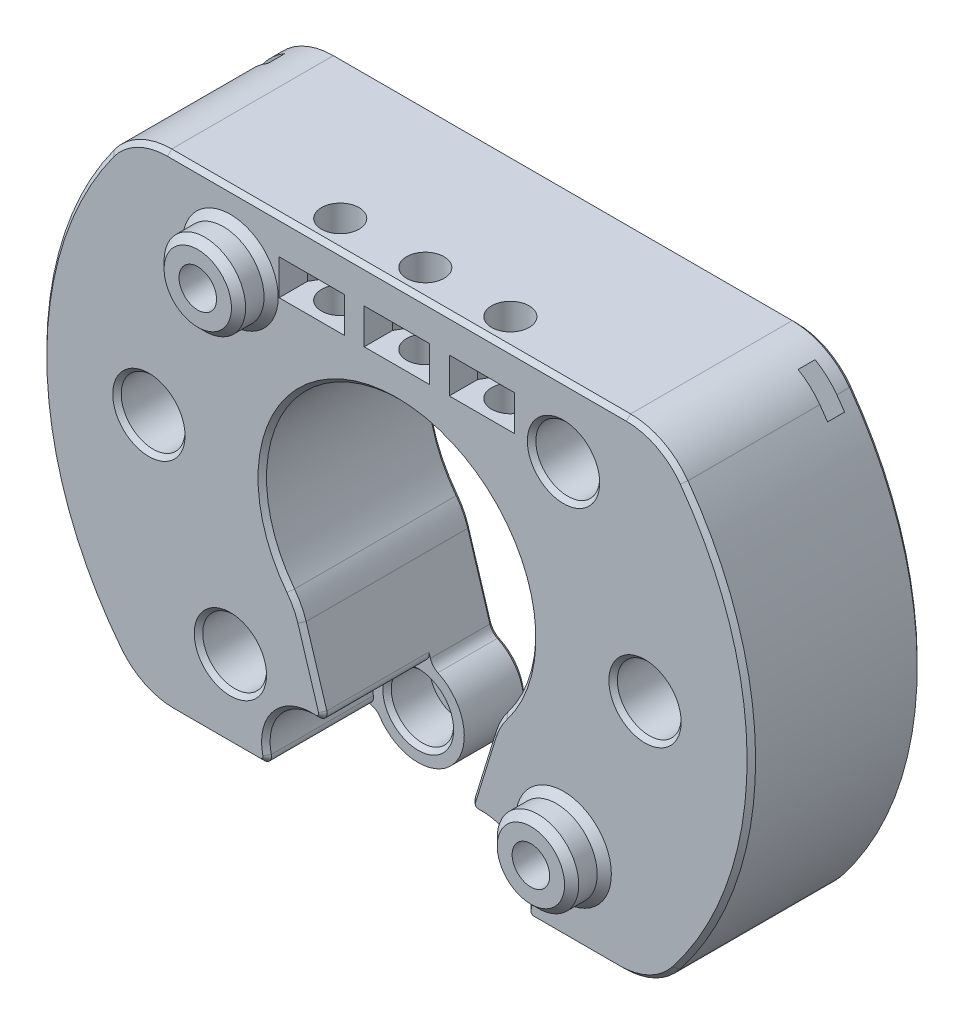
SolidWorks part; units mm, degrees
ref_plane "Ebene vorne" through (0, 0, 0) normal (0, 0, 1) x (1, 0, 0)
ref_plane "Ebene oben" through (0, 0, 0) normal (0, 1, 0) x (1, 0, 0)
ref_plane "Ebene rechts" through (0, 0, 0) normal (1, 0, 0) x (0, 0, -1)
sketch "Skizze1" plane through (0, 0, 0) normal (0, 0, 1) x (1, 0, 0)
  line L0 (0, 15.499) -> (0, -28.3741) construction
  line L1 (0, 33.5) -> (-37.1181, 33.5)
  line L2 (0, 33.5) -> (37.1181, 33.5)
  line L3 (-36, -34.6987) -> (-36, -65)
  line L4 (-36, -65) -> (0, -65)
  line L5 (-50, 78.1636) -> (-50, -33.9451) construction
  line L6 (50, 78.1636) -> (50, -33.9451) construction
  line L7 (-50, 0) -> (50, 0) construction
  line L8 (36, -34.6987) -> (36, -65)
  line L10 (0, -65) -> (36, -65)
  line L11 (-17.9133, -34.6987) -> (-36, -34.6987)
  line L12 (-23.5, 23.5) -> (23.5, 23.5) construction
  line L13 (-23.5, 23.5) -> (-23.5, -23.5) construction
  line L14 (-23.5, -23.5) -> (23.5, -23.5) construction
  line L15 (23.5, 23.5) -> (23.5, -23.5) construction
  line L18 (-14, -12.8452) -> (-10, -25.8153)
  line L19 (14, -12.8452) -> (10, -25.8153)
  line L22 (36, -34.6987) -> (17.9133, -34.6987)
  arc A0 (-37.1181, 33.5) -> (-36, -34.6987) centre (0, 0) ccw
  circle A1 centre (0, 0) radius 19
  arc A3 (37.1181, 33.5) -> (36, -34.6987) centre (0, 0) cw
  circle A4 centre (-23.5, 23.5) radius 4.5
  circle A5 centre (23.5, 23.5) radius 4.5
  circle A6 centre (23.5, -23.5) radius 4.5
  circle A7 centre (-23.5, -23.5) radius 4.5
  arc A8 (-10, -25.8153) -> (-17.9133, -34.6987) centre (-12, -32) cw
  arc A9 (10, -25.8153) -> (17.9133, -34.6987) centre (12, -32) ccw
  circle A10 centre (23.5, -23.5) radius 4.5
  point P18 (0, 0)
  point P37 (-23.5, 0)
  point P38 (0, 23.5)
  dimension "D1" = 72
  dimension "D4" = 38
  dimension "D2" = 47
  dimension "D7" = 9
  dimension "D8" = 28
  dimension "D13" = 32
  dimension "D10" = 6.5
  dimension "D3" = 65
  dimension "D5" = 33.5
  dimension "D6" = 100
  dimension "D9" = 24
  dimension "D14" = 20
extrude "Aufsatz-Linear austragen1" add sketch "Skizze1" along normal blind 24 contours L19 A9 L22 A3 L2 L1 A0 A8 L18 A1 A7 A6 A5 A4 region at (18.559, 32.2678, 0)
sketch "Skizze2" plane through (0, 0, 24) normal (0, 0, 1) x (1, 0, 0)
  line L3 (0, 0) -> (0, -32) construction
  circle A0 centre (12, -32) radius 6.5
  arc A1 (10, -25.8153) -> (17.9133, -34.6987) centre (12, -32) ccw construction
  circle A3 centre (-12, -32) radius 6.5
  arc A4 (-17.9133, -34.6987) -> (-10, -25.8153) centre (-12, -32) ccw construction
extrude "Schnitt-Linear austragen1" cut sketch "Skizze2" against normal blind 15
sketch "Skizze3" plane through (0, 0, 9) normal (0, 0, 1) x (1, 0, 0)
  circle A0 centre (12, -32) radius 4.4
  circle A1 centre (-12, -32) radius 4.4
  dimension "D1" = 8.8
extrude "Schnitt-Linear austragen2" cut sketch "Skizze3" against normal blind 6
sketch "Skizze4" plane through (0, 0, 24) normal (0, 0, 1) x (1, 0, 0)
  circle A0 centre (-23.5, 23.5) radius 5.75
  circle A1 centre (23.5, -23.5) radius 5.75
  circle A6 centre (-23.5, 23.5) radius 2.65
  circle A7 centre (23.5, -23.5) radius 2.65
  dimension "D1" = 11.5
  dimension "D2" = 5.3
extrude "Aufsatz-Linear austragen2" add sketch "Skizze4" along normal blind 4.6 and the other way blind 2
sketch "Skizze8" plane through (0, 33.5, 0) normal (0, 1, 0) x (1, 0, 0)
  line L0 (-37.1181, -24) -> (37.1181, -24) construction
  line L1 (4.6188, -20) -> (2.3094, -16)
  line L2 (2.3094, -16) -> (-2.3094, -16)
  line L3 (-2.3094, -16) -> (-4.6188, -20)
  line L4 (-4.6188, -20) -> (-2.3094, -24) construction
  line L5 (-2.3094, -24) -> (2.3094, -24) construction
  line L6 (2.3094, -24) -> (4.6188, -20) construction
  line L7 (-4.6188, -20) -> (-4.6188, -24)
  line L8 (-4.6188, -24) -> (4.6188, -24)
  line L9 (4.6188, -24) -> (4.6188, -20)
  line L10 (0, 0) -> (0, -24) construction
  line L11 (-37.1181, 0) -> (37.1181, 0) construction
  line L18 (16.6188, -20) -> (14.3094, -16)
  line L19 (14.3094, -16) -> (9.6906, -16)
  line L20 (9.6906, -16) -> (7.3812, -20)
  line L21 (7.3812, -20) -> (7.3812, -24)
  line L22 (7.3812, -24) -> (16.6188, -24)
  line L23 (16.6188, -24) -> (16.6188, -20)
  line L24 (7.3812, -20) -> (9.6906, -24) construction
  line L25 (9.6906, -24) -> (14.3094, -24) construction
  line L26 (14.3094, -24) -> (16.6188, -20) construction
  line L27 (4.6188, -20) -> (16.6188, -20) construction
  line L28 (-7.3812, -20) -> (-9.6906, -16)
  line L29 (-9.6906, -16) -> (-14.3094, -16)
  line L30 (-14.3094, -16) -> (-16.6188, -20)
  line L31 (-16.6188, -20) -> (-16.6188, -24)
  line L32 (-16.6188, -24) -> (-7.3812, -24)
  line L33 (-7.3812, -24) -> (-7.3812, -20)
  line L34 (-16.6188, -20) -> (-14.3094, -24) construction
  line L35 (-14.3094, -24) -> (-9.6906, -24) construction
  line L36 (-9.6906, -24) -> (-7.3812, -20) construction
  line L37 (4.6188, -20) -> (-7.3812, -20) construction
  circle A0 centre (0, -20) radius 4 construction
  circle A1 centre (12, -20) radius 4 construction
  circle A2 centre (-12, -20) radius 4 construction
  dimension "D1" = 8
  dimension "D2" = 2
  dimension "D3" = 12
  dimension "D4" = 12
extrude "Schnitt-Linear austragen6" cut sketch "Skizze8" against normal blind 5 from offset 5 offset against normal yes
sketch "Skizze9" plane through (0, 33.5, 0) normal (0, 1, 0) x (1, 0, 0)
  circle A0 centre (-12, -20) radius 2.65
  circle A1 centre (0, -20) radius 2.65
  circle A2 centre (12, -20) radius 2.65
  dimension "D1" = 5.3
extrude "Schnitt-Linear austragen7" cut sketch "Skizze9" against normal blind 30
sketch "Skizze12" plane through (0, 0, 0) normal (0, 0, -1) x (-1, 0, 0)
  line L0 (0, 0) -> (0, 33.5) construction
  line L1 (37.1181, 33.5) -> (-37.1181, 33.5) construction
  circle A0 centre (-35, 25.5) radius 1.65
  circle A1 centre (35, 25.5) radius 1.65
  dimension "D1" = 3.3
  dimension "D2" = 70
  dimension "D3" = 8
extrude "Schnitt-Linear austragen9" cut sketch "Skizze12" against normal blind 16
sketch "Skizze11" plane through (0, 0, 0) normal (0, 0, -1) x (-1, 0, 0)
  line L0 (0, 0) -> (0, 33.5) construction
  line L1 (37.1181, 33.5) -> (-37.1181, 33.5) construction
  line L2 (-44.8995, 39.6421) -> (-30.7574, 25.5)
  line L3 (-30.7574, 25.5) -> (-35, 21.2574)
  line L4 (-44.8995, 39.6421) -> (-49.1421, 35.3995)
  line L5 (-49.1421, 35.3995) -> (-35, 21.2574)
  line L6 (44.8995, 39.6421) -> (49.1421, 35.3995)
  line L7 (44.8995, 39.6421) -> (30.7574, 25.5)
  line L8 (30.7574, 25.5) -> (35, 21.2574)
  line L9 (49.1421, 35.3995) -> (35, 21.2574)
  dimension "D1" = 45
  dimension "D2" = 6
  dimension "D3" = 20
extrude "Schnitt-Linear austragen8" cut sketch "Skizze11" against normal blind 2.4 from offset 2.4 offset against normal yes
sketch "Skizze13" plane through (0, 0, 24) normal (0, 0, 1) x (1, 0, 0)
  line L0 (0, 33.5) -> (0, 0) construction
  line L1 (-37.1181, 33.5) -> (37.1181, 33.5) construction
  circle A0 centre (35, 0) radius 4.5
  circle A1 centre (-35, 0) radius 4.5
  dimension "D1" = 70
  dimension "D2" = 9
extrude "Schnitt-Linear austragen10" cut sketch "Skizze13" against normal up to next
chamfer "Fase1" distance 1 angle 45 4 edges at (29.25, -23.5, 28.6) (-17.75, 23.5, 28.6) (29.25, -23.5, 24) (-17.75, 23.5, 24)
fillet "Verrundung1" radius 10 6 edges at (-37.1181, 33.5, 12) (37.1181, 33.5, 12) (36, -34.6987, 12) (-36, -34.6987, 12) (14, -12.8452, 12) (-14, -12.8452, 12)
fillet "Verrundung2" radius 1 4 edges at (17.9133, -34.6987, 16.5) (-17.9133, -34.6987, 16.5) (-10, -25.8153, 16.5) (10, -25.8153, 16.5)
fillet "Verrundung4" radius 2 4 edges at (17.9133, -34.6987, 4.5) (10, -25.8153, 4.5) (-10, -25.8153, 4.5) (-17.9133, -34.6987, 4.5)
chamfer "Fase2" distance 0.6 angle 45 26 edges at (16.9372, -27.7723, 24) (25.3845, -34.6987, 24) (49.9912, -0.9388, 24) (0, 33.5, 24) (0, 19, 24) (-25.3845, -34.6987, 24) (-49.9912, -0.9388, 24) (35.8373, -33.6917, 24) (36.9104, 32.4093, 24) (-36.9104, 32.4093, 24) (-35.8373, -33.6917, 24) (28, 23.5, 24) (-19, -23.5, 24) (16.4, -32, 9) (18.522, -34.3206, 24) (11.9495, -19.4941, 24) (10.6637, -25.1437, 24) (-11.9495, -19.4941, 24) (-10.6637, -25.1437, 24) (-16.9372, -27.7723, 24) (-18.522, -34.3206, 24) (-7.6, -32, 9) (14.0856, -13.1092, 24) (-14.0856, -13.1092, 24) (39.5, 0, 24) (-39.5, 0, 24)
chamfer "Fase3" distance 0.6 angle 45 28 edges at (-35.8373, -33.6917, 0) (-25.2735, -34.6987, 0) (-7.0841, -36.2525, 0) (-11.845, -19.833, 0) (0, 19, 0) (11.845, -19.833, 0) (7.0841, -36.2525, 0) (25.2735, -34.6987, 0) (35.8373, -33.6917, 0) (49.9912, -0.9388, 0) (36.9104, 32.4093, 0) (0, 33.5, 0) (-36.9104, 32.4093, 0) (-49.9912, -0.9388, 0) (-19, 23.5, 0) (28, 23.5, 0) (28, -23.5, 0) (-19, -23.5, 0) (-14.0856, -13.1092, 0) (14.0856, -13.1092, 0) (9.8811, -25.6243, 0) (18.1375, -34.9364, 0) (-18.1375, -34.9364, 0) (-9.8811, -25.6243, 0) (-33.35, 25.5, 0) (33.35, 25.5, 0) (-30.5, 0, 0) (39.5, 0, 0)
